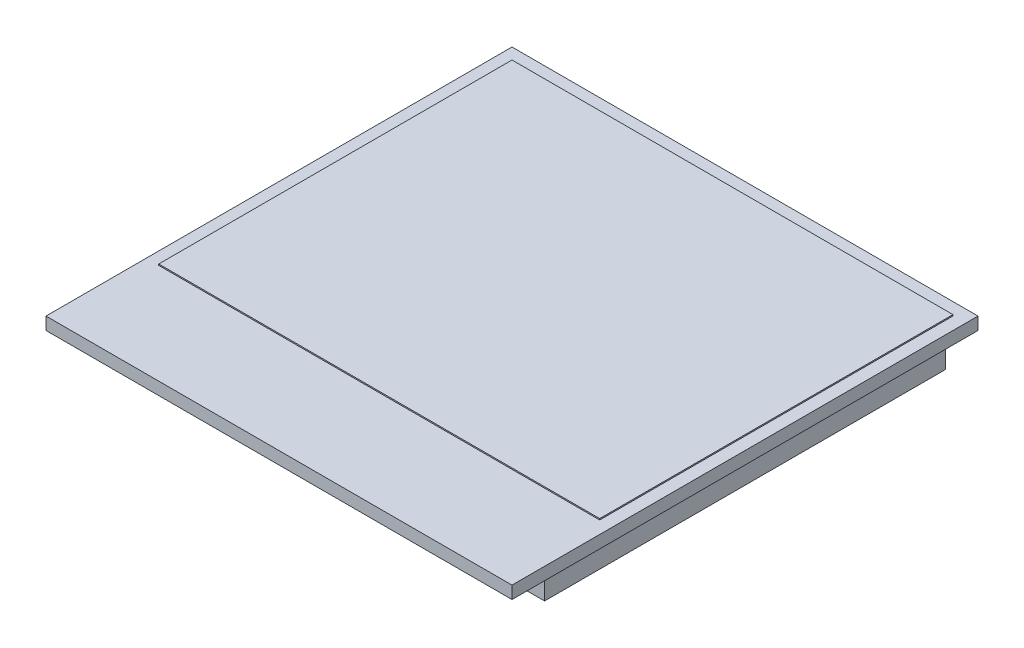
SolidWorks part; units mm, degrees
ref_plane "Front Plane" through (0, 0, 0) normal (0, 0, 1) x (1, 0, 0)
ref_plane "Top Plane" through (0, 0, 0) normal (0, 1, 0) x (1, 0, 0)
ref_plane "Right Plane" through (0, 0, 0) normal (1, 0, 0) x (0, 0, -1)
sketch "Sketch1" plane through (0, 0, 0) normal (0, 1, 0) x (1, 0, 0)
  line L1 (-9.3, 0) -> (9.3, 0)
  line L2 (-9.3, 0) -> (-9.3, 18.6)
  line L3 (-9.3, 18.6) -> (9.3, 18.6)
  line L4 (9.3, 0) -> (9.3, 18.6)
  point P4 (0, 0)
  dimension "D1" = 18.6
  dimension "D2" = 18.6
extrude "glass" add sketch "Sketch1" along normal blind 0.5
sketch "Sketch2" plane through (0, 0.5, 0) normal (0, 1, 0) x (1, 0, 0)
  line L0 (0, 4) -> (0, 0) construction
  line L1 (-8.8, 18.1) -> (8.8, 18.1)
  line L2 (-8.8, 18.1) -> (-8.8, 4)
  line L3 (-8.8, 4) -> (8.8, 4)
  line L4 (8.8, 18.1) -> (8.8, 4)
  line L5 (-9.3, 0) -> (9.3, 0) construction
  line L6 (-9.3, 18.6) -> (-9.3, 0) construction
  line L7 (9.3, 18.6) -> (-9.3, 18.6) construction
  dimension "D1" = 4
  dimension "D2" = 0.5
  dimension "D3" = 0.5
extrude "display" add sketch "Sketch2" along normal blind 0.05 separate body
sketch "Sketch3" plane through (0, 0, 0) normal (0, -1, 0) x (1, 0, 0)
  line L0 (0, 0) -> (0, -2.6) construction
  line L1 (-8, -2.6) -> (8, -2.6)
  line L2 (-8, -2.6) -> (-8, -18.6)
  line L3 (-8, -18.6) -> (8, -18.6)
  line L4 (8, -2.6) -> (8, -18.6)
  line L5 (-9.3, 0) -> (9.3, 0) construction
  line L6 (9.3, -18.6) -> (-9.3, -18.6) construction
  dimension "D1" = 16
  dimension "D2" = 16
extrude "sticky_foam" add sketch "Sketch3" along normal blind 2 separate body
